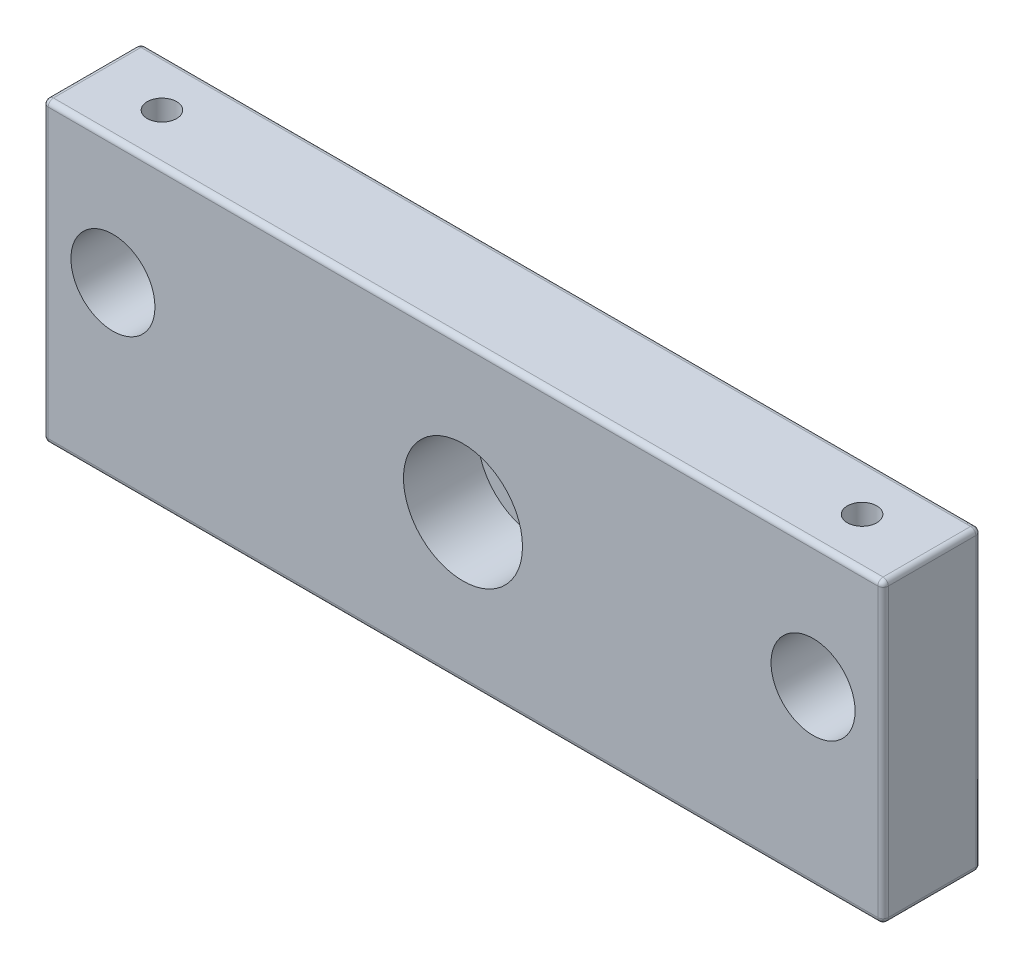
SolidWorks part; units mm, degrees
ref_plane "Front Plane" through (0, 0, 0) normal (0, 0, 1) x (1, 0, 0)
ref_plane "Top Plane" through (0, 0, 0) normal (0, 1, 0) x (1, 0, 0)
ref_plane "Right Plane" through (0, 0, 0) normal (1, 0, 0) x (0, 0, -1)
sketch "Sketch1" plane through (0, 0, 0) normal (0, 0, 1) x (1, 0, 0)
  line L1 (-60, -21.25) -> (60, -21.25)
  line L2 (-60, -21.25) -> (-60, 21.25)
  line L3 (-60, 21.25) -> (60, 21.25)
  line L4 (60, -21.25) -> (60, 21.25)
  line L5 (-60, -21.25) -> (60, 21.25) construction
  line L6 (-60, 21.25) -> (60, -21.25) construction
  point P0 (0, 0)
  dimension "D1" = 120
  dimension "D2" = 42.5
extrude "Boss-Extrude1" add sketch "Sketch1" along normal mid plane 14
sketch "Sketch2" plane through (0, 0, 7) normal (0, 0, 1) x (1, 0, 0)
  circle A0 centre (0, 0) radius 8.5
  dimension "D1" = 17
extrude "Cut-Extrude1" cut sketch "Sketch2" against normal blind 10.6
sketch "Sketch3" plane through (0, 0, -3.6) normal (0, 0, 1) x (1, 0, 0)
  circle A0 centre (0, 0) radius 4
  dimension "D1" = 8
extrude "Cut-Extrude2" cut sketch "Sketch3" against normal through all
sketch "Sketch5" plane through (0, 0, 7) normal (0, 0, 1) x (1, 0, 0)
  line L0 (-40.6477, 3.4) -> (36.4799, 3.4) construction
  circle A0 centre (-50, 3.4) radius 6
  circle A1 centre (50, 3.4) radius 6
  dimension "D1" = 12
  dimension "D2" = 12
  dimension "D4" = 50
  dimension "D3" = 50
  dimension "D5" = 3.4
extrude "Cut-Extrude4" cut sketch "Sketch5" against normal through all
sketch "Sketch6" plane through (0, -21.25, 0) normal (0, -1, 0) x (1, 0, 0)
  line L0 (-60, 0) -> (60, 0) construction
  line L1 (-60, 7) -> (-60, -7) construction
  line L2 (60, 7) -> (60, -7) construction
  circle A0 centre (-50, 0) radius 2.1
  circle A1 centre (-25, 0) radius 2.1
  circle A2 centre (25, 0) radius 2.1
  circle A3 centre (50, 0) radius 2.1
  circle A4 centre (-37.5, 0) radius 1.25
  circle A5 centre (37.5, 0) radius 1.25
  dimension "D1" = 4.2
  dimension "D2" = 4.2
  dimension "D3" = 4.2
  dimension "D4" = 4.2
  dimension "D5" = 10
  dimension "D9" = 2.5
  dimension "D10" = 2.5
  dimension "D11" = 22.5
  dimension "D12" = 22.5
  dimension "D6" = 35
  dimension "D7" = 10
  dimension "D8" = 35
extrude "Cut-Extrude5" cut sketch "Sketch6" against normal blind 10
fillet "Fillet1" radius 0.75 12 edges at (60, 21.25, 0) (60, 0, -7) (0, 21.25, -7) (60, 0, 7) (60, -21.25, 0) (0, -21.25, -7) (0, 21.25, 7) (-60, 21.25, 0) (-60, 0, -7) (0, -21.25, 7) (-60, -21.25, 0) (-60, 0, 7)
sketch "Sketch7" plane through (0, 21.25, 0) normal (0, 1, 0) x (1, 0, 0)
  line L0 (-1000, 0) -> (49000, 0) construction
  circle A0 centre (-50, 0) radius 2.1
  circle A1 centre (50, 0) radius 2.1
  dimension "D1" = 50
  dimension "D2" = 50
  dimension "D3" = 4.2
  dimension "D4" = 4.2
extrude "Cut-Extrude6" cut sketch "Sketch7" against normal up to next
